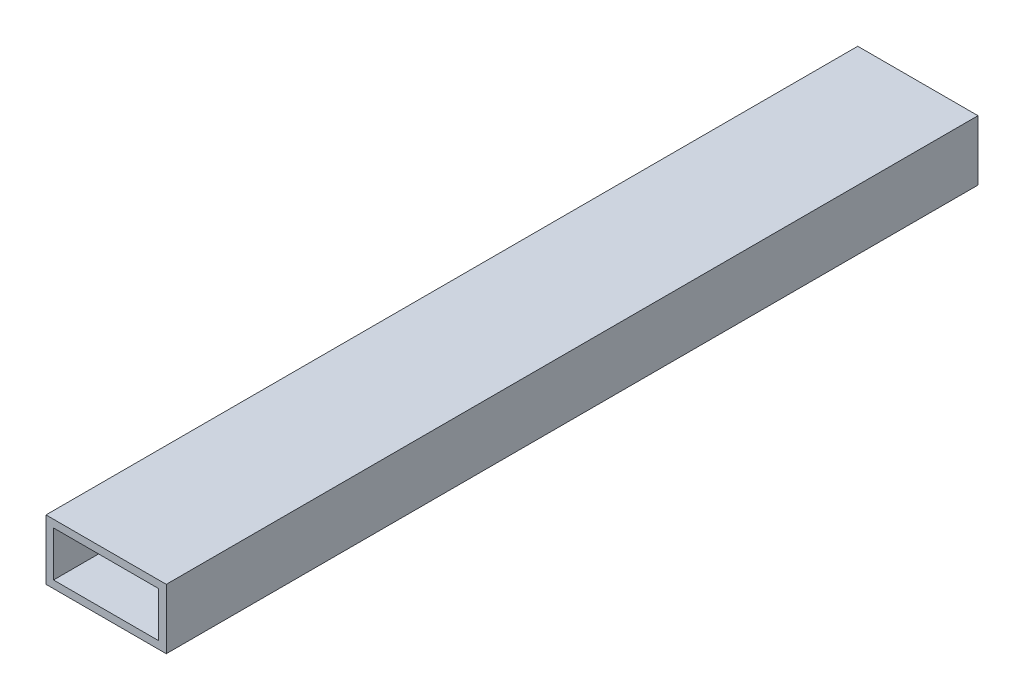
SolidWorks part; units mm, degrees
material "6061-T6 (SS)"
ref_plane "Front Plane" through (0, 0, 0) normal (0, 0, 1) x (1, 0, 0)
ref_plane "Top Plane" through (0, 0, 0) normal (0, 1, 0) x (1, 0, 0)
ref_plane "Right Plane" through (0, 0, 0) normal (1, 0, 0) x (0, 0, -1)
sketch "Sketch1" plane through (0, 0, 0) normal (0, 1, 0) x (1, 0, 0)
  line L1 (0, 0) -> (50.8, 0)
  line L2 (0, 0) -> (0, 342.9)
  line L3 (0, 342.9) -> (50.8, 342.9)
  line L4 (50.8, 0) -> (50.8, 342.9)
  dimension "D1" = 50.8
  dimension "D2" = 342.9
extrude "Boss-Extrude1" add sketch "Sketch1" along normal blind 25.4
shell "Shell1" thickness 3.175 removed face at (25.4, 12.7, -342.9) removed face at (25.4, 12.7, 0)
